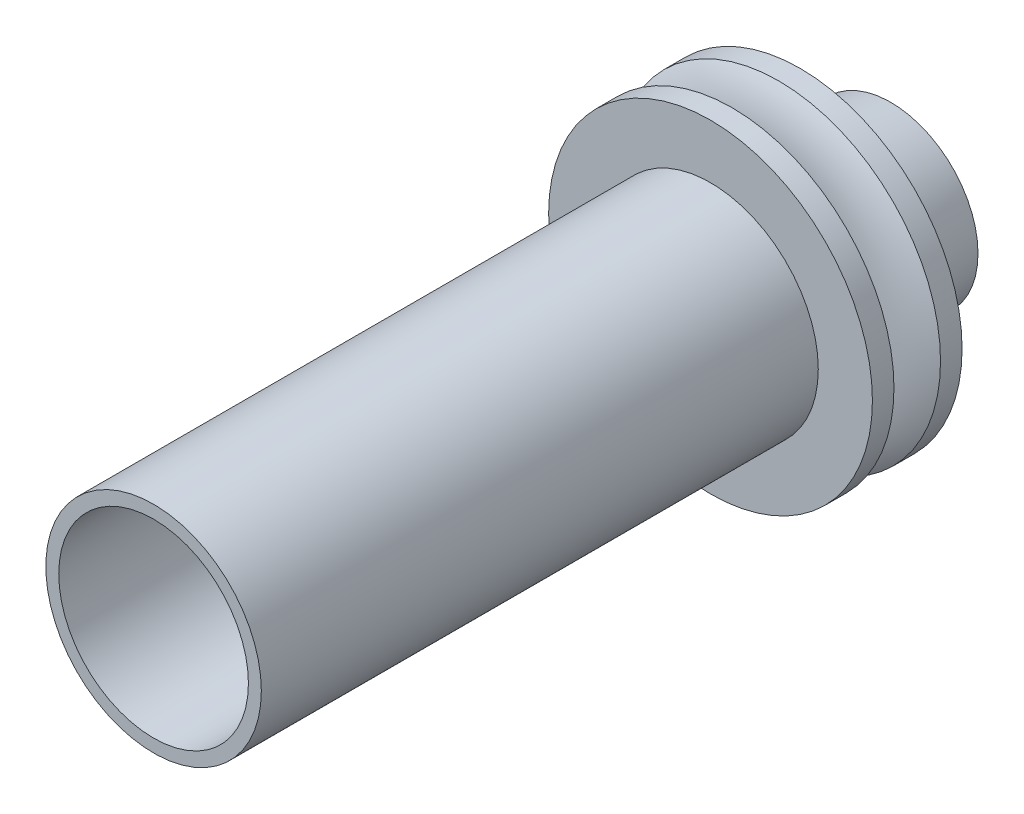
SolidWorks part; units mm, degrees
ref_plane "Front Plane" through (0, 0, 0) normal (0, 0, 1) x (1, 0, 0)
ref_plane "Top Plane" through (0, 0, 0) normal (0, 1, 0) x (1, 0, 0)
ref_plane "Right Plane" through (0, 0, 0) normal (1, 0, 0) x (0, 0, -1)
ref_axis "Axis1" through (0, 0, -29.6946) along (0, 0, 1)
sketch "Sketch3" plane through (0, 0, 0) normal (1, 0, 0) x (0, 0, -1)
  line L0 (-144.8554, 25) -> (5.1446, 25)
  line L2 (-32.9596, 0) -> (31.8386, 0) construction
  line L3 (26.1446, 20.2502) -> (26.1446, 0)
  line L4 (26.1446, 0) -> (-144.8554, 0)
  line L5 (-144.8554, 0) -> (-144.8554, 25)
  line L7 (6.1446, 22) -> (26.1446, 20.2502)
  line L8 (6.1446, 22) -> (5.1446, 22)
  line L9 (5.1446, 22) -> (5.1446, 25)
  dimension "D1" = 50
  dimension "D2" = 1
  dimension "D3" = 5
  dimension "D4" = 20
  dimension "D5" = 150
revolve "Revolve1" add sketch "Sketch3" angle 360 about L2
shell "Shell1" thickness 3 removed face at (25, 0, 144.8554) removed face at (20.2502, 0, -26.1446)
sketch "Sketch4" plane through (0, 0, 0) normal (1, 0, 0) x (0, 0, -1)
  line L15 (-5.2554, 26.3328) -> (-5.2554, 52.5292) construction
  line B0 (-15.6554, 37.5579) -> (-15.6554, 25)
  line B1 (-7.6554, 26.3328) -> (-2.8554, 26.3328)
  line B2 (-15.6554, 37.5579) -> (-10.6554, 37.5579)
  line B3 (-15.6554, 25) -> (5.1446, 25)
  line B4 (5.1446, 37.5579) -> (0.1446, 37.5579)
  line B5 (-5.2554, 26.3328) -> (-5.2554, 25) construction
  line B6 (5.1446, 37.5579) -> (5.1446, 25)
  arc B7 (-10.6554, 37.5579) -> (-7.6554, 26.3328) centre (-30.1558, 26.3328) cw
  arc B8 (0.1446, 37.5579) -> (-2.8554, 26.3328) centre (19.6451, 26.3328) ccw
sketch_block_instance "Block5-2"
sketch_block "Block5" parameters "D1"=5, "D2"=2.4
revolve "Revolve3" add sketch "Sketch4" angle 360 about axis through (0, 0, -29.6946) along (0, 0, 1)
